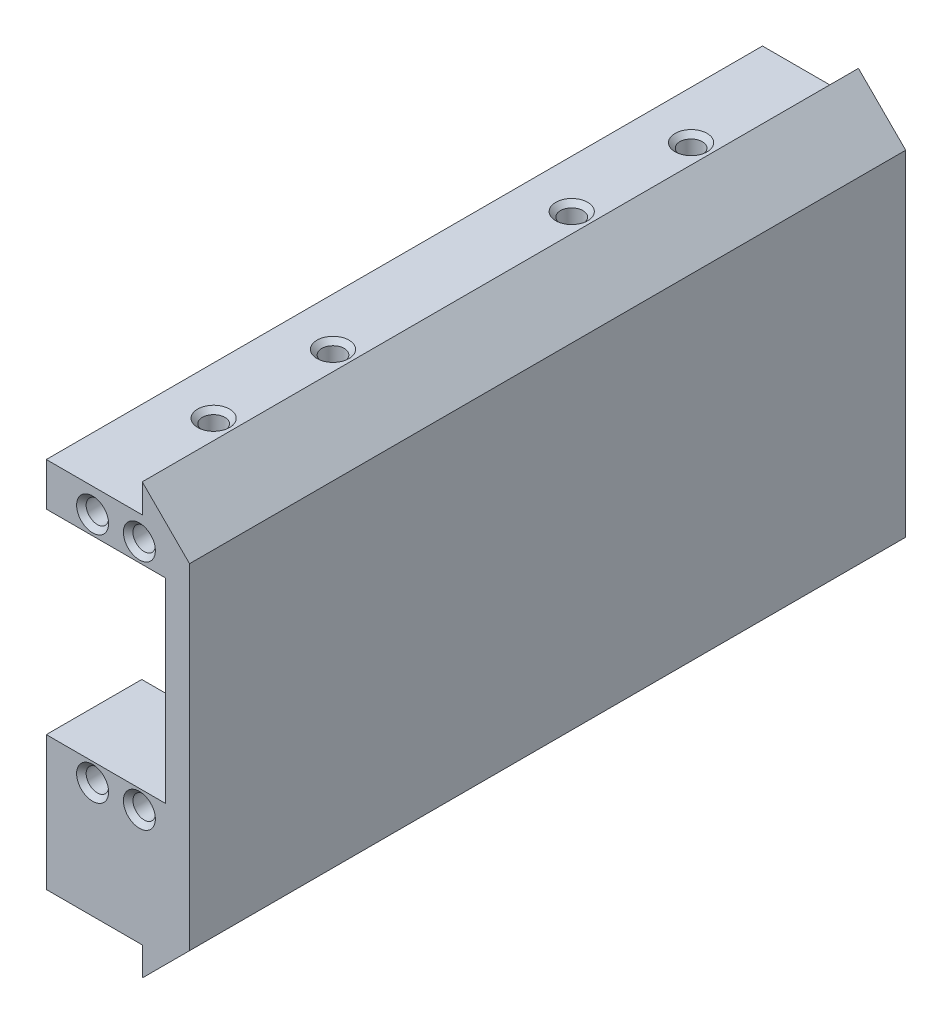
SolidWorks part; units mm, degrees
material "ABS"
ref_plane "Front Plane" through (0, 0, 0) normal (0, 0, 1) x (1, 0, 0)
ref_plane "Top Plane" through (0, 0, 0) normal (0, 1, 0) x (1, 0, 0)
ref_plane "Right Plane" through (0, 0, 0) normal (1, 0, 0) x (0, 0, -1)
sketch "Sketch1" plane through (0, 0, 0) normal (0, 0, 1) x (1, 0, 0)
  line L0 (-15, 45) -> (15, 45)
  line L1 (-15, 45) -> (15, 45) construction
  line L2 (-15, 45) -> (-15, -45) construction
  line L3 (-15, -45) -> (15, -45) construction
  line L4 (15, 45) -> (15, -45) construction
  line L5 (-15, 45) -> (15, -45) construction
  line L6 (-15, -45) -> (15, 45) construction
  line L7 (15, 45) -> (15, -45)
  line L8 (15, -45) -> (-15, -45)
  line L9 (-15, -45) -> (-15, -10.9)
  line L10 (-15, -10.9) -> (10, -10.9)
  line L11 (10, -10.9) -> (10, 30)
  line L12 (10, 30) -> (-15, 30)
  line L13 (-15, 30) -> (-15, 45)
  point P0 (0, 0)
  dimension "D1" = 90
  dimension "D2" = 30
  dimension "D3" = 40.9
  dimension "D4" = 15
  dimension "D5" = 5
extrude "Boss-Extrude1" add sketch "Sketch1" along normal blind 150
sketch "Sketch2" plane through (0, 0, 150) normal (0, 0, 1) x (1, 0, 0)
  line L0 (10, 30) -> (-10.8, 30) construction
  line L1 (-15, 30) -> (10, 30) construction
  line L2 (-0.4, 30) -> (-0.4, 33.89) construction
  line L3 (-0.4, 33.89) -> (4.5, 33.89) construction
  line L4 (10, 30) -> (10, -10.9) construction
  line L5 (10, 9.55) -> (15, 9.55) construction
  line L7 (15, -45) -> (15, 45) construction
  circle A0 centre (4.5, 33.89) radius 2.35
  circle A1 centre (-5.3, 33.89) radius 2.35
  circle A4 centre (4.5, -14.79) radius 2.35
  circle A5 centre (-5.3, -14.79) radius 2.35
  dimension "D4" = 4.7
  dimension "D1" = 20.8
  dimension "D2" = 3.89
  dimension "D3" = 4.9
extrude "Cut-Extrude1" cut sketch "Sketch2" against normal blind 8
sketch "Sketch3" plane through (0, 0, 0) normal (0, 0, -1) x (-1, 0, 0)
  line L0 (-10, 30) -> (10.8, 30) construction
  line L1 (15, 30) -> (-10, 30) construction
  line L2 (-10, 30) -> (-10, -10.9) construction
  line L3 (-10, 9.55) -> (-15, 9.55) construction
  line L5 (0.4, 30) -> (0.4, 33.89) construction
  line L6 (0.4, 33.89) -> (-4.5, 33.89) construction
  line L7 (-15, -45) -> (-15, 45) construction
  circle A0 centre (-4.5, 33.89) radius 2.35
  circle A1 centre (5.3, 33.89) radius 2.35
  circle A4 centre (-4.5, -14.79) radius 2.35
  circle A5 centre (5.3, -14.79) radius 2.35
  dimension "D4" = 4.7
  dimension "D1" = 20.8
  dimension "D2" = 3.89
  dimension "D3" = 4.9
extrude "Cut-Extrude2" cut sketch "Sketch3" against normal blind 8
chamfer "Chamfer1" distance 1 angle 45 8 edges at (2.15, 33.89, 0) (-2.95, 33.89, 0) (-7.65, 33.89, 150) (6.85, 33.89, 150) (2.15, -14.79, 150) (-2.95, -14.79, 150) (-7.65, -14.79, 0) (6.85, -14.79, 0)
sketch "Sketch4" plane through (0, 0, 150) normal (0, 0, 1) x (1, 0, 0)
  line L0 (0, 0) -> (15, 0) construction
  line L1 (-15, -45) -> (5.1, -45)
  line L2 (-15, -45) -> (-15, -39)
  line L3 (-15, -39) -> (5.1, -39)
  line L4 (5.1, -45) -> (5.1, -39)
  line L5 (15, -45) -> (15, 45) construction
  line L6 (-15, 39) -> (5.1, 39)
  line L7 (5.1, 45) -> (5.1, 39)
  line L8 (-15, 45) -> (5.1, 45)
  line L9 (-15, 45) -> (-15, 39)
  dimension "D1" = 6
  dimension "D2" = 20.1
extrude "Cut-Extrude3" cut sketch "Sketch4" against normal through all
chamfer "Chamfer2" distance 9.9 angle 45 2 edges at (15, -45, 75) (15, 45, 75)
sketch "Sketch5" plane through (0, 39, 0) normal (0, 1, 0) x (1, 0, 0)
  line L0 (-4.95, 0) -> (-4.95, -25) construction
  line L1 (-15, 0) -> (5.1, 0) construction
  line L2 (-4.95, -25) -> (-4.95, -50) construction
  line L3 (-4.95, -50) -> (-4.95, -75) construction
  line L4 (-4.95, -100) -> (-4.95, -125) construction
  line L5 (-4.95, -125) -> (-4.95, -150) construction
  line L6 (-15, -150) -> (5.1, -150) construction
  line L8 (-4.95, -75) -> (-4.95, -100) construction
  line L10 (5.1, 0) -> (-15, 0) construction
  line L11 (5.1, 0) -> (5.1, -150) construction
  line L12 (5.1, -150) -> (-15, -150) construction
  line L13 (-15, 0) -> (-15, -150) construction
  circle A0 centre (-4.95, -25) radius 2.35
  circle A1 centre (-4.95, -50) radius 2.35
  circle A2 centre (-4.95, -100) radius 2.35
  circle A3 centre (-4.95, -125) radius 2.35
  dimension "D1" = 4.7
  dimension "D2" = 4.7
  dimension "D3" = 4.7
  dimension "D4" = 4.7
  dimension "D5" = 20.1
  dimension "D6" = 150
extrude "Cut-Extrude4" cut sketch "Sketch5" against normal blind 8
chamfer "Chamfer3" distance 1 angle 45 4 edges at (-4.95, 39, 127.35) (-4.95, 39, 102.35) (-4.95, 39, 52.35) (-4.95, 39, 27.35)
sketch "Sketch6" plane through (0, -39, 0) normal (0, -1, 0) x (1, 0, 0)
  line L1 (5, 121) -> (-15, 121) construction
  line L2 (5, 121) -> (5, 29) construction
  line L3 (5, 29) -> (-15, 29) construction
  line L4 (-15, 121) -> (-15, 29) construction
  line L5 (-15, 0) -> (-15, 150) construction
  line L6 (5.1, 150) -> (-15, 150) construction
  line L7 (5.1, 0) -> (-15, 0) construction
  line L8 (-5, 121) -> (-5, 90.3333) construction
  line L9 (-5, 90.3333) -> (-5, 59.6667) construction
  line L10 (-5, 59.6667) -> (-5, 29) construction
  circle A0 centre (-5, 59.6667) radius 6.1
  circle A1 centre (-5, 90.3333) radius 6.1
  dimension "D3" = 12.2
  dimension "D4" = 12.2
  dimension "D1" = 29
  dimension "D2" = 29
  dimension "D5" = 10
  dimension "D6" = 10
  dimension "D7" = 20
extrude "Cut-Extrude5" cut sketch "Sketch6" against normal blind 3.2
sketch "Sketch8" plane through (-15, 0, 0) normal (-1, 0, 0) x (0, 0, 1)
  line L0 (150, -10.9) -> (130, -10.9) construction
  line L1 (150, -10.9) -> (0, -10.9) construction
  line L2 (0, -10.9) -> (20, -10.9) construction
  line L3 (150, -10.9) -> (0, -10.9) construction
  line L5 (20, -10.9) -> (130, -10.9)
  line L6 (20, -10.9) -> (20, -32.8)
  line L7 (20, -32.8) -> (130, -32.8)
  line L8 (130, -10.9) -> (130, -32.8)
  line L9 (53.5667, -35.8) -> (65.7667, -35.8) construction
  dimension "D1" = 20
  dimension "D2" = 20
  dimension "D3" = 3
extrude "Cut-Extrude7" cut sketch "Sketch8" against normal up to surface (25 mm away) up to face at (10, 9.55, 75)
fillet "Fillet1" radius 0.2 2 edges at (-5, -39, 84.2333) (-5, -39, 53.5667)
